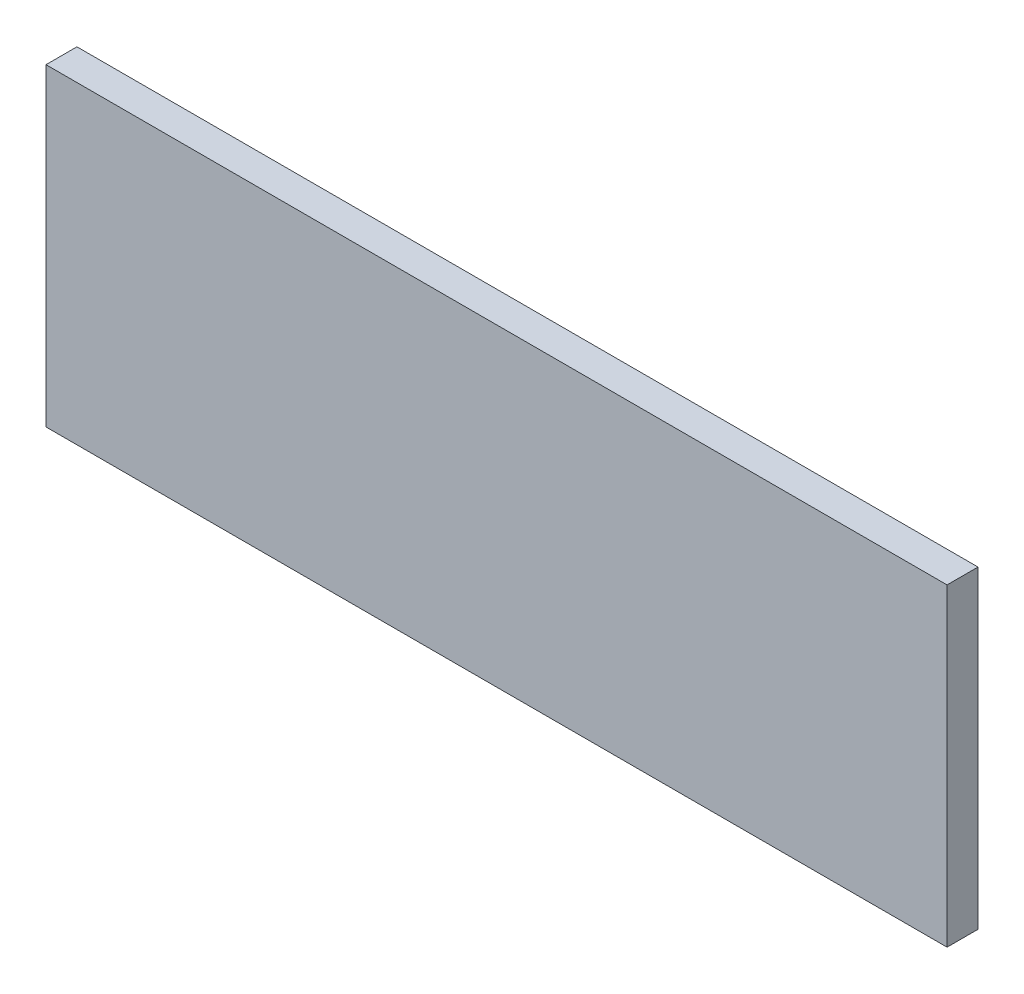
SolidWorks part; units mm, degrees
ref_plane "Front Plane" through (0, 0, 0) normal (0, 0, 1) x (1, 0, 0)
ref_plane "Top Plane" through (0, 0, 0) normal (0, 1, 0) x (1, 0, 0)
ref_plane "Right Plane" through (0, 0, 0) normal (1, 0, 0) x (0, 0, -1)
sketch "Sketch2" plane through (0, 0, 0) normal (0, 0, 1) x (1, 0, 0)
  line L1 (-46.228, -16.0972) -> (46.228, -16.0972)
  line L2 (-46.228, -16.0972) -> (-46.228, 16.0973)
  line L3 (-46.228, 16.0973) -> (46.228, 16.0973)
  line L4 (46.228, -16.0972) -> (46.228, 16.0973)
  line L5 (-46.228, -16.0972) -> (46.228, 16.0973) construction
  line L6 (-46.228, 16.0973) -> (46.228, -16.0972) construction
  point P0 (0, 0)
  dimension "D1" = 92.456
  dimension "D2" = 32.1945
extrude "Boss-Extrude1" add sketch "Sketch2" along normal blind 3.175
